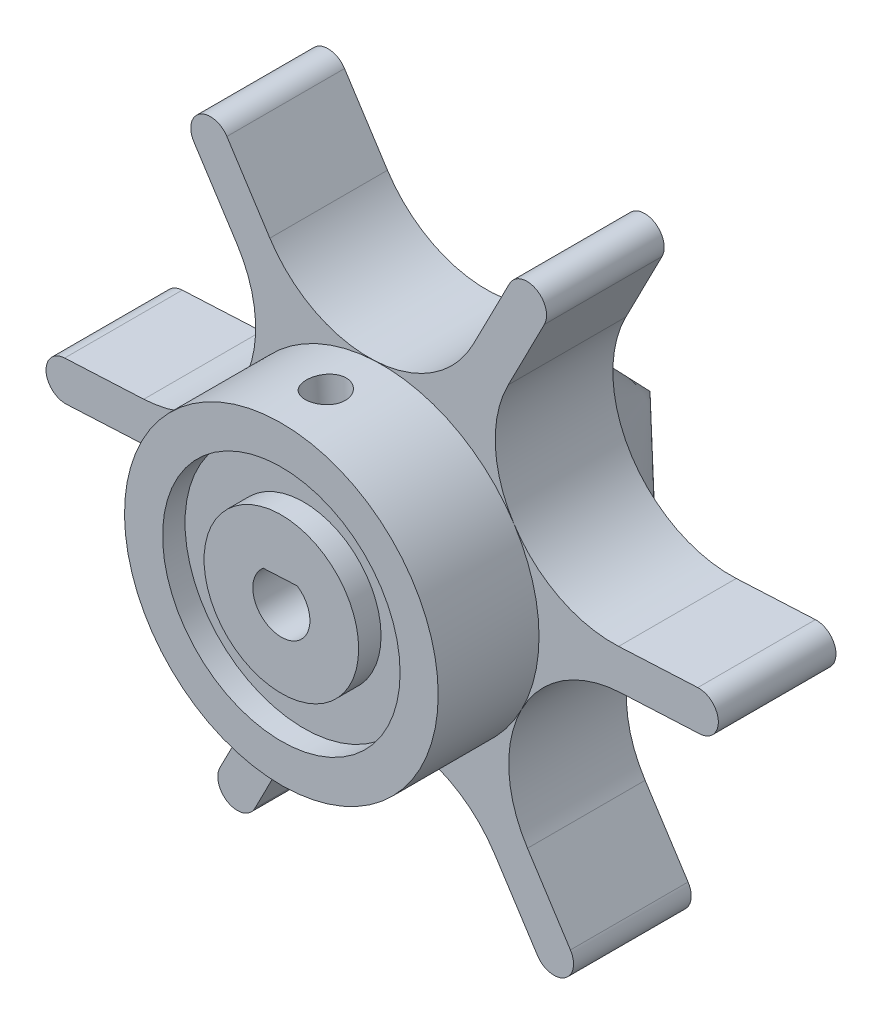
SolidWorks part; units mm, degrees
ref_plane "Front Plane" through (0, 0, 0) normal (0, 0, 1) x (1, 0, 0)
ref_plane "Top Plane" through (0, 0, 0) normal (0, 1, 0) x (1, 0, 0)
ref_plane "Right Plane" through (0, 0, 0) normal (1, 0, 0) x (0, 0, -1)
sketch "Sketch1" plane through (0, 0, 0) normal (0, 0, 1) x (1, 0, 0)
  line L0 (-33.6058, 45.6534) -> (-25.9397, 33.7658)
  line L1 (-30.6644, 47.5503) -> (-56.5119, -2.781) construction
  line L2 (-56.5119, -2.781) -> (-25.8475, -50.3313) construction
  line L3 (-25.8475, -50.3313) -> (30.6644, -47.5503) construction
  line L4 (30.6644, -47.5503) -> (56.5119, 2.781) construction
  line L5 (56.5119, 2.781) -> (25.8475, 50.3313) construction
  line L6 (25.8475, 50.3313) -> (-30.6644, 47.5503) construction
  line L7 (-27.723, 49.4471) -> (-20.0569, 37.5596)
  line L8 (22.7341, 51.9302) -> (16.2722, 39.3474)
  line L9 (28.961, 48.7324) -> (22.4991, 36.1496)
  line L10 (56.3399, 6.2768) -> (42.2119, 5.5815)
  line L11 (56.684, -0.7147) -> (42.556, -1.41)
  line L12 (33.6058, -45.6534) -> (25.9397, -33.7658)
  line L13 (27.723, -49.4471) -> (20.0569, -37.5596)
  line L14 (-22.7341, -51.9302) -> (-16.2722, -39.3474)
  line L15 (-28.961, -48.7324) -> (-22.4991, -36.1496)
  line L16 (-56.3399, -6.2768) -> (-42.2119, -5.5815)
  line L17 (-56.684, 0.7147) -> (-42.556, 1.41)
  circle A0 centre (41.1797, 26.5562) radius 21 construction
  circle A1 centre (43.5882, -22.3846) radius 21 construction
  circle A2 centre (2.4085, -48.9408) radius 21 construction
  circle A3 centre (-41.1797, -26.5562) radius 21 construction
  circle A4 centre (-43.5882, 22.3846) radius 21 construction
  circle A5 centre (-2.4085, 48.9408) radius 21 construction
  circle A6 centre (0, 0) radius 49 construction
  circle A7 centre (-30.6644, 47.5503) radius 3.5
  circle A8 centre (25.8475, 50.3313) radius 3.5
  circle A9 centre (56.5119, 2.781) radius 3.5
  circle A10 centre (30.6644, -47.5503) radius 3.5
  circle A11 centre (-25.8475, -50.3313) radius 3.5
  circle A12 centre (-56.5119, -2.781) radius 3.5
  arc A13 (-42.556, 1.41) -> (-25.9397, 33.7658) centre (-43.5882, 22.3846) ccw
  arc A14 (-20.0569, 37.5596) -> (16.2722, 39.3474) centre (-2.4085, 48.9408) ccw
  arc A15 (22.4991, 36.1496) -> (42.2119, 5.5815) centre (41.1797, 26.5562) ccw
  arc A16 (42.556, -1.41) -> (25.9397, -33.7658) centre (43.5882, -22.3846) ccw
  arc A17 (20.0569, -37.5596) -> (-16.2722, -39.3474) centre (2.4085, -48.9408) ccw
  arc A18 (-22.4991, -36.1496) -> (-42.2119, -5.5815) centre (-41.1797, -26.5562) ccw
  point P25 (0, 0)
  point P36 (0, 0)
  point P60 (0, 0)
  point P77 (0, 0)
  dimension "D2" = 42
  dimension "D4" = 7
  dimension "D1" = 6
  dimension "D3" = 6
  dimension "D5" = 6
  dimension "D6" = 6
extrude "Boss-Extrude1" add sketch "Sketch1" along normal blind 21 contours A18 L15 A11 L14 A17 L13 A10 L12 A16 L11 A9 L10 A15 L9 A8 L8 A14 L7 A7 L0 A13 L17 A12 L16 | A12 | A7 | A8 | A9 | A10 | A11 region at (0, 0, 0) region at (-30.6644, 47.5503, 0) region at (-56.5119, -2.781, 0) region at (25.8475, 50.3313, 0) region at (-25.8475, -50.3313, 0) region at (56.5119, 2.781, 0) region at (30.6644, -47.5503, 0)
ref_plane "Plane1" through (0, 0, 0) normal (0.0492, -0.9988, 0) x (-0.9988, -0.0492, 0)
sketch "Sketch3" plane through (0, 0, 0) normal (0.0492, -0.9988, 0) x (-0.9988, -0.0492, 0)
  line L0 (0, 0) -> (-28, 0)
  line L1 (-28, 0) -> (0, 26.8135)
  line L2 (0, 26.8135) -> (0, 0)
  dimension "D1" = 28
revolve "Revolve1" add sketch "Sketch3" angle 360 about L2
sketch "Sketch4" plane through (0, 0, 21) normal (0, 0, 1) x (1, 0, 0)
  circle A0 centre (0, 0) radius 28
extrude "Boss-Extrude2" add sketch "Sketch4" along normal blind 18
sketch "Sketch5" plane through (0, 0, 39) normal (0, 0, 1) x (1, 0, 0)
  line L0 (-3.231, 3.946) -> (2.828, 4.2441)
  line L1 (56.3399, 6.2768) -> (42.2119, 5.5815) construction
  circle A0 centre (0, 0) radius 5.1
  circle A1 centre (0, 0) radius 4.1 construction
  dimension "D1" = 10.2
  dimension "D2" = 8.2
sketch "Sketch6" plane through (0, 0, 39) normal (0, 0, 1) x (1, 0, 0)
  circle A0 centre (0, 0) radius 17.5 construction
  circle A1 centre (0, 0) radius 21.2
  circle A2 centre (0, 0) radius 13.8
  dimension "D1" = 35
  dimension "D2" = 3.7
  dimension "D3" = 3.7
extrude "Cut-Extrude1" cut sketch "Sketch6" against normal blind 4 contours A2 | A1 region at (0, 0, 39)
extrude "Cut-Extrude2" cut sketch "Sketch5" against normal blind 20 contours L0 A0 region at (0.0118, -0.2395, 39)
sketch "Sketch7" plane through (-0.2015, 4.095, 0) normal (0.0492, -0.9988, 0) x (0.9988, 0.0492, 0)
  line L0 (28, 39) -> (-28, 39) construction
  circle A0 centre (0, 29.7) radius 1.75
  dimension "D2" = 3.5
  dimension "D1" = 9.3
extrude "Cut-Extrude3" cut sketch "Sketch7" against normal through all and the other way through all
ref_plane "Plane2" through (-1.3763, 27.9662, 0) normal (-0.0492, 0.9988, 0) x (0.9988, 0.0492, 0)
sketch "Sketch8" plane through (-1.3763, 27.9662, 0) normal (-0.0492, 0.9988, 0) x (0.9988, 0.0492, 0)
  circle A0 centre (0, -29.7) radius 3.5
  dimension "D1" = 7
extrude "Cut-Extrude4" cut sketch "Sketch8" against normal blind 5.5
ref_plane "Plane5" through (1.3763, -27.9662, 0) normal (0.0492, -0.9988, 0) x (-0.9988, -0.0492, 0)
